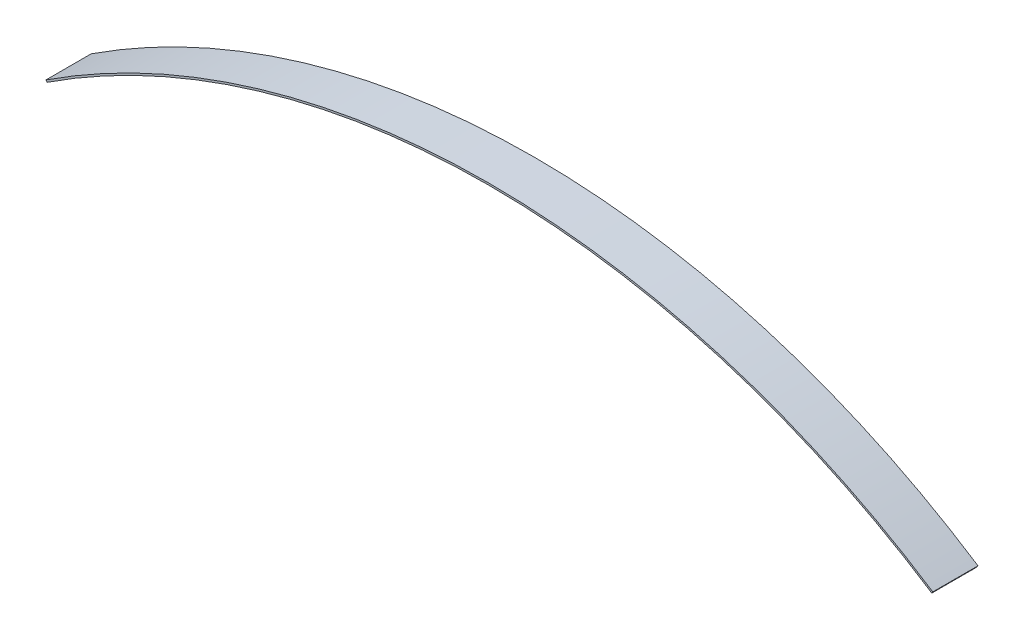
SolidWorks part; units mm, degrees
ref_plane "Спереди" through (0, 0, 0) normal (0, 0, 1) x (1, 0, 0)
ref_plane "Сверху" through (0, 0, 0) normal (0, 1, 0) x (1, 0, 0)
ref_plane "Справа" through (0, 0, 0) normal (1, 0, 0) x (0, 0, -1)
sketch "Эскиз1" plane through (0, 0, 0) normal (0, 0, 1) x (1, 0, 0)
  line L0 (0, 0) -> (71.2504, 0) construction
  line L1 (-91.2893, -35) -> (36.5786, -35) construction
  arc A0 (-99.3098, -35) -> (135.6902, -35) centre (18.1902, -214.7321) cw
  dimension "D1" = 35
  dimension "D2" = 235
extrude "Вытянуть-Тонкостенный1" add sketch "Эскиз1" along normal blind 12 thin thin type one direction reverse wall 0.5
